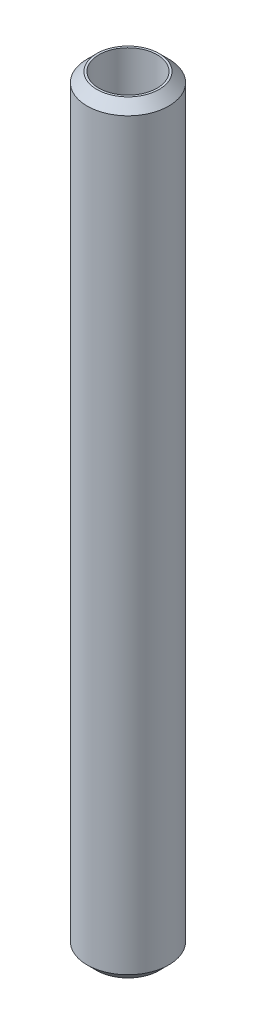
SolidWorks part; units mm, degrees
ref_plane "Front Plane" through (0, 0, 0) normal (0, 0, 1) x (1, 0, 0)
ref_plane "Top Plane" through (0, 0, 0) normal (0, 1, 0) x (1, 0, 0)
ref_plane "Right Plane" through (0, 0, 0) normal (1, 0, 0) x (0, 0, -1)
sketch "Sketch1" plane through (0, 0, 0) normal (0, 1, 0) x (1, 0, 0)
  circle A0 centre (0, 0) radius 17.5
  dimension "SHAFT_OD" = 35
extrude "Boss-Extrude1" add sketch "Sketch1" along normal blind 327.4717
sketch "Sketch2" plane through (0, 0, 0) normal (0, 1, 0) x (1, 0, 0)
  circle A0 centre (0, 0) radius 12.4667
  dimension "BORE_D" = 24.9334
extrude "Cut-Extrude1" cut sketch "Sketch2" along normal through all
chamfer "Chamfer1" distance 4.1229 angle 45 2 edges at (0, 327.4717, 17.5) (0, 0, 17.5)
